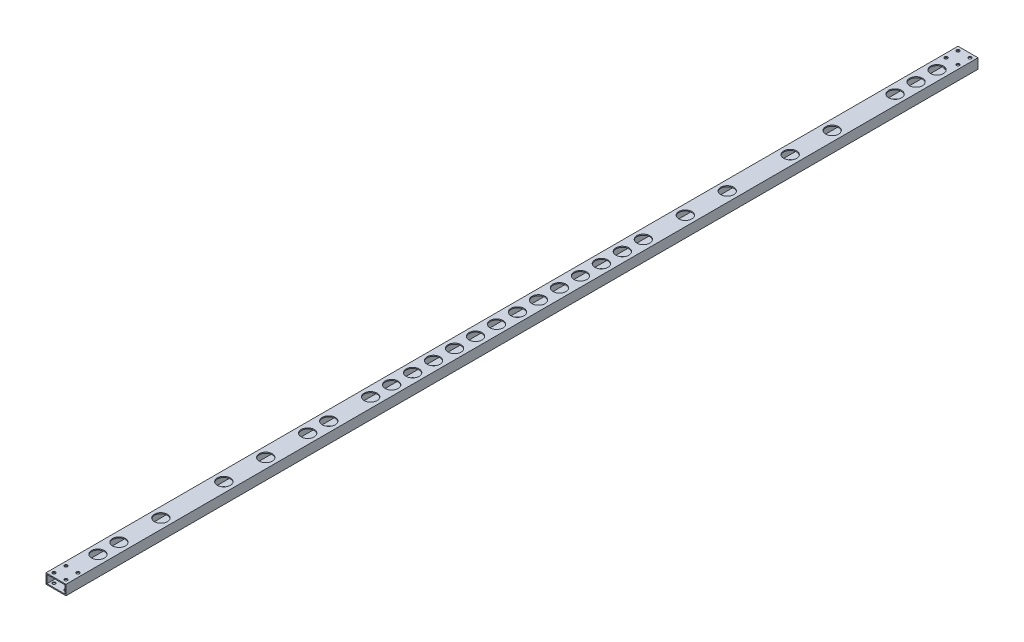
SolidWorks part; units mm, degrees
material "1100-H18 棒材(SS)"
ref_plane "前视基准面" through (0, 0, 0) normal (0, 0, 1) x (1, 0, 0)
ref_plane "上视基准面" through (0, 0, 0) normal (0, 1, 0) x (1, 0, 0)
ref_plane "右视基准面" through (0, 0, 0) normal (1, 0, 0) x (0, 0, -1)
other "Configuration Table"
sketch "草图1" plane through (0, 0, 0) normal (0, 0, 1) x (1, 0, 0)
  line L1 (0, 0) -> (20, 0)
  line L2 (0, 0) -> (0, 10)
  line L3 (0, 10) -> (20, 10)
  line L4 (20, 0) -> (20, 10)
  line L5 (1, 1) -> (19, 1)
  line L6 (1, 1) -> (1, 9)
  line L7 (1, 9) -> (19, 9)
  line L8 (19, 1) -> (19, 9)
  dimension "D1" = 20
  dimension "D2" = 10
  dimension "D3" = 1
  dimension "D4" = 1
  dimension "D5" = 1
  dimension "D6" = 1
extrude "凸台-拉伸1" add sketch "草图1" along normal blind 913
sketch "草图2" plane through (0, 0, 0) normal (0, -1, 0) x (1, 0, 0)
  circle A1 centre (5, 726) radius 1.6
  circle A2 centre (5, 726) radius 1.6
  circle A3 centre (5, 193) radius 1.6
  circle A5 centre (5, 762) radius 1.6
  circle A6 centre (5, 762) radius 1.6
  circle A7 centre (5, 193) radius 1.6
  circle A9 centre (5, 798) radius 1.6
  circle A10 centre (5, 798) radius 1.6
  circle A11 centre (5, 615) radius 1.6
  circle A12 centre (5, 615) radius 1.6
  circle A15 centre (5, 834) radius 1.6
  circle A16 centre (5, 834) radius 1.6
  circle A19 centre (5, 687) radius 1.6
  circle A20 centre (5, 687) radius 1.6
  circle A21 centre (5, 229) radius 1.6
  circle A23 centre (5, 690) radius 1.6
  circle A24 centre (5, 690) radius 1.6
  circle A25 centre (5, 229) radius 1.6
  circle A31 centre (5, 265) radius 1.6
  circle A32 centre (5, 265) radius 1.6
  circle A33 centre (5, 82) radius 1.6
  circle A34 centre (5, 82) radius 1.6
  circle A37 centre (5, 301) radius 1.6
  circle A38 centre (5, 301) radius 1.6
  circle A41 centre (5, 154) radius 1.6
  circle A42 centre (5, 154) radius 1.6
  circle A45 centre (5, 157) radius 1.6
  circle A46 centre (5, 157) radius 1.6
  dimension "D1" = 0
  dimension "D2" = 0
  dimension "D3" = 0
  dimension "D5" = 0
  dimension "D6" = 0
  dimension "D7" = 0
  dimension "D8" = 0
  dimension "D10" = 0
  dimension "D11" = 0
  dimension "D12" = 0
  dimension "D13" = 0
  dimension "D16" = 0
  dimension "D18" = 0
  dimension "D20" = 0
extrude "切除-拉伸1" cut sketch "草图2" against normal through all rebuild error yes
sketch "草图3" plane through (0, 10, 0) normal (0, 1, 0) x (1, 0, 0)
  line L0 (20, -913) -> (20, 0) construction
  line L1 (20, 0) -> (0, 0) construction
  circle A0 centre (10, -10) radius 6.5 construction
  circle A1 centre (10, -31) radius 6.5
  circle A2 centre (10, -52) radius 6.5
  circle A3 centre (10, -73) radius 6.5
  circle A4 centre (10, -94) radius 6.5 [skipped]
  circle A5 centre (10, -115) radius 6.5 [skipped]
  circle A6 centre (10, -136) radius 6.5
  circle A7 centre (10, -157) radius 6.5 [skipped]
  circle A8 centre (10, -178) radius 6.5
  circle A9 centre (10, -199) radius 6.5 [skipped]
  circle A10 centre (10, -220) radius 6.5 [skipped]
  circle A11 centre (10, -241) radius 6.5
  circle A12 centre (10, -262) radius 6.5 [skipped]
  circle A13 centre (10, -283) radius 6.5
  circle A14 centre (10, -304) radius 6.5 [skipped]
  circle A15 centre (10, -325) radius 6.5
  circle A16 centre (10, -346) radius 6.5
  circle A17 centre (10, -367) radius 6.5
  circle A18 centre (10, -388) radius 6.5
  circle A19 centre (10, -409) radius 6.5
  circle A20 centre (10, -430) radius 6.5
  circle A21 centre (10, -451) radius 6.5
  circle A22 centre (10, -472) radius 6.5
  circle A23 centre (10, -493) radius 6.5
  circle A24 centre (10, -514) radius 6.5
  circle A25 centre (10, -535) radius 6.5
  circle A26 centre (10, -556) radius 6.5
  circle A27 centre (10, -577) radius 6.5
  circle A28 centre (10, -598) radius 6.5
  circle A29 centre (10, -619) radius 6.5 [skipped]
  circle A30 centre (10, -640) radius 6.5
  circle A31 centre (10, -661) radius 6.5
  circle A32 centre (10, -682) radius 6.5 [skipped]
  circle A33 centre (10, -703) radius 6.5
  circle A34 centre (10, -724) radius 6.5 [skipped]
  circle A35 centre (10, -745) radius 6.5
  circle A36 centre (10, -766) radius 6.5 [skipped]
  circle A37 centre (10, -787) radius 6.5 [skipped]
  circle A38 centre (10, -808) radius 6.5
  circle A39 centre (10, -829) radius 6.5 [skipped]
  circle A40 centre (10, -850) radius 6.5
  circle A41 centre (10, -871) radius 6.5
  circle A42 centre (10, -892) radius 6.5 construction
  dimension "D1" = 13
  dimension "D2" = 10
  dimension "D3" = 10
  dimension "D5" = 21
  dimension "D4" = 43
extrude "切除-拉伸2" cut sketch "草图3" against normal through all
sketch "草图4" plane through (0, 10, 0) normal (0, 1, 0) x (1, 0, 0)
  circle A1 centre (16, -909) radius 1.575
  circle A2 centre (16, -909) radius 1.575
  circle A3 centre (4, -909) radius 1.575
  circle A4 centre (4, -909) radius 1.575
  circle A5 centre (4, -897) radius 1.575
  circle A6 centre (4, -897) radius 1.575
  circle A7 centre (16, -897) radius 1.575
  circle A8 centre (16, -897) radius 1.575
  circle A9 centre (16, -929) radius 1.575
  circle A10 centre (16, -929) radius 1.575 construction
  circle A11 centre (16, -917) radius 1.575
  circle A12 centre (16, -917) radius 1.575 construction
  circle A13 centre (26, -929) radius 1.575
  circle A14 centre (26, -929) radius 1.575 construction
  circle A15 centre (26, -917) radius 1.575
  circle A16 centre (26, -917) radius 1.575 construction
  circle A17 centre (4, -917) radius 1.575
  circle A18 centre (4, -917) radius 1.575 construction
  circle A19 centre (4, -929) radius 1.575
  circle A20 centre (4, -929) radius 1.575 construction
  circle A21 centre (-6, -929) radius 1.575
  circle A22 centre (-6, -929) radius 1.575 construction
  circle A23 centre (-6, -917) radius 1.575
  circle A24 centre (-6, -917) radius 1.575 construction
  circle A25 centre (16, -4) radius 1.575
  circle A26 centre (16, -4) radius 1.575
  circle A27 centre (4, -4) radius 1.575
  circle A28 centre (4, -4) radius 1.575
  circle A29 centre (4, -16) radius 1.575
  circle A30 centre (4, -16) radius 1.575
  circle A31 centre (16, -16) radius 1.575
  circle A32 centre (16, -16) radius 1.575
  circle A33 centre (16, 16) radius 1.575
  circle A34 centre (16, 16) radius 1.575 construction
  circle A35 centre (16, 4) radius 1.575
  circle A36 centre (16, 4) radius 1.575 construction
  circle A37 centre (26, 16) radius 1.575
  circle A38 centre (26, 16) radius 1.575 construction
  circle A39 centre (26, 4) radius 1.575
  circle A40 centre (26, 4) radius 1.575 construction
  circle A41 centre (4, 4) radius 1.575
  circle A42 centre (4, 4) radius 1.575 construction
  circle A43 centre (4, 16) radius 1.575
  circle A44 centre (4, 16) radius 1.575 construction
  circle A45 centre (-6, 16) radius 1.575
  circle A46 centre (-6, 16) radius 1.575 construction
  circle A47 centre (-6, 4) radius 1.575
  circle A48 centre (-6, 4) radius 1.575 construction
  dimension "D1" = 0
  dimension "D2" = 0
  dimension "D3" = 0
  dimension "D4" = 0
  dimension "D5" = 0
  dimension "D6" = 0
  dimension "D7" = 0
  dimension "D8" = 0
  dimension "D9" = 0
  dimension "D10" = 0
  dimension "D11" = 0
  dimension "D12" = 0
  dimension "D13" = 0
  dimension "D14" = 0
  dimension "D15" = 0
  dimension "D16" = 0
  dimension "D17" = 0
  dimension "D18" = 0
  dimension "D19" = 0
  dimension "D20" = 0
  dimension "D21" = 0
  dimension "D22" = 0
  dimension "D23" = 0
  dimension "D24" = 0
extrude "切除-拉伸3" cut sketch "草图4" against normal through all
